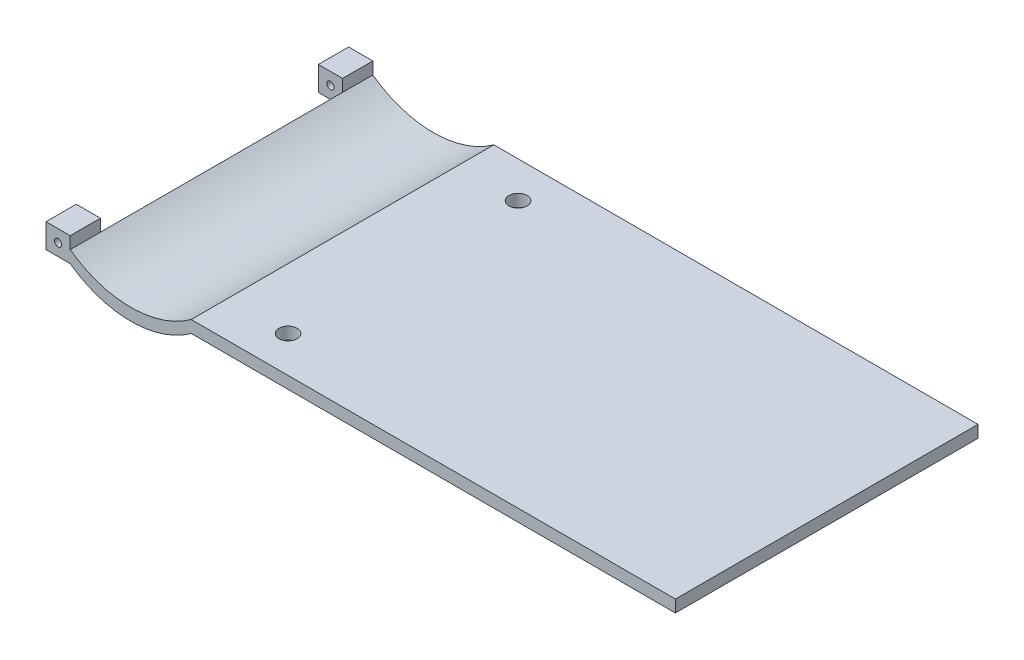
SolidWorks part; units mm, degrees
material "PBT 一般用途"
ref_plane "前视基准面" through (0, 0, 0) normal (0, 0, 1) x (1, 0, 0)
ref_plane "上视基准面" through (0, 0, 0) normal (0, 1, 0) x (1, 0, 0)
ref_plane "右视基准面" through (0, 0, 0) normal (1, 0, 0) x (0, 0, -1)
sketch "草图1" plane through (0, 0, 0) normal (0, 0, 1) x (1, 0, 0)
  line L1 (400, -10) -> (-400, -10)
  line L2 (400, -10) -> (400, 10)
  line L3 (400, 10) -> (-400, 10)
  line L4 (-400, -10) -> (-400, 10)
  line L5 (400, -10) -> (-400, 10) construction
  line L6 (400, 10) -> (-400, -10) construction
  line L7 (-600, -10) -> (-640, -10)
  line L8 (-600, -10) -> (-600, 30)
  line L9 (-600, 10) -> (-600, -10)
  line L10 (-600, 30) -> (-640, 30)
  line L11 (-640, -10) -> (-640, 30)
  arc A0 (-600, -10) -> (-400, -10) centre (-500, 127.4773) ccw
  arc A1 (-600, 10) -> (-400, 10) centre (-500, 147.4773) ccw
  circle A2 centre (-620, 10) radius 6
  point P0 (0, 0)
  dimension "D3" = 170
  dimension "D4" = 170
  dimension "D1" = 800
  dimension "D2" = 20
  dimension "D5" = 200
  dimension "D6" = 20
  dimension "D7" = 40
  dimension "D8" = 40
extrude "凸台-拉伸1" add sketch "草图1" along normal blind 500 contours L4 L1 L2 L3 | A1 A0 L4 | L11 L7 L8 L10 A2 region at (0, 0, 0) region at (-500, -40.4549, 0) region at (-620, -9.4343, 0)
sketch "草图5" plane through (0, 10, 0) normal (0, 1, 0) x (1, 0, 0)
  line L0 (-400, -250) -> (-286.9738, -250) construction
  line L3 (-400, -500) -> (-400, 0) construction
  line L4 (400, 0) -> (-400, 0) construction
  circle A0 centre (-300, -60) radius 15
  circle A1 centre (-300, -440) radius 15
  circle A2 centre (-300, -440) radius 15
  dimension "D1" = 100
  dimension "D3" = 30
  dimension "D2" = 60
extrude "切除-拉伸2" cut sketch "草图5" against normal through all contours A1 | A0 region at (-300, 10, 60) region at (-300, 10, 440)
sketch "草图6" plane through (0, 30, 0) normal (0, 1, 0) x (1, 0, 0)
  line L0 (-600, -500) -> (-600, 0) construction
  line L1 (-600, -50) -> (-640, -50)
  line L2 (-600, -50) -> (-600, -450)
  line L3 (-600, -450) -> (-640, -450)
  line L4 (-640, -50) -> (-640, -450)
  line L5 (-640, -500) -> (-640, 0) construction
  line L6 (-600, 0) -> (-640, 0) construction
  dimension "D1" = 400
  dimension "D2" = 50
extrude "切除-拉伸3" cut sketch "草图6" against normal through all
